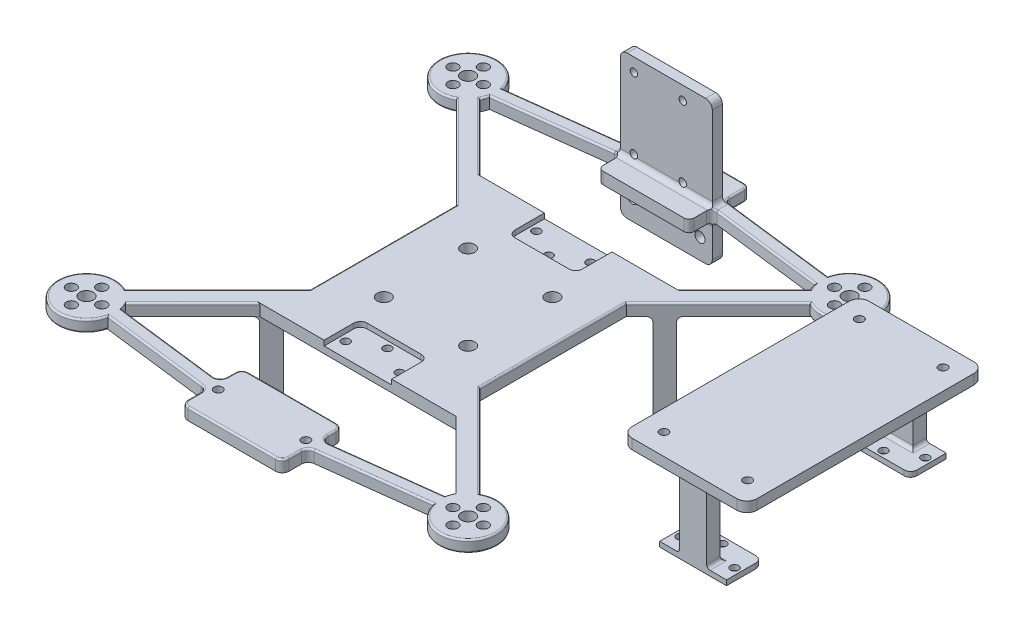
SolidWorks part; units mm, degrees
ref_plane "Front Plane" through (0, 0, 0) normal (0, 0, 1) x (1, 0, 0)
ref_plane "Top Plane" through (0, 0, 0) normal (0, 1, 0) x (1, 0, 0)
ref_plane "Right Plane" through (0, 0, 0) normal (1, 0, 0) x (0, 0, -1)
sketch "Sketch1" plane through (0, 0, 0) normal (0, 1, 0) x (1, 0, 0)
  line L10 (25.2228, 21.7178) -> (52.5194, 49.0143)
  line L11 (29.1718, 32.6991) -> (49.0032, 52.5305)
  line L14 (25.2228, -21.7245) -> (52.5163, -49.018)
  line L15 (29.1386, -32.6991) -> (48.9964, -52.5569)
  line L19 (-25.2228, 21.7178) -> (-52.5879, 49.0829)
  line L20 (-29.1386, -32.6991) -> (-49.0885, -52.649)
  line L22 (-25.2228, -21.7245) -> (-52.6084, -49.1101)
  line L33 (-25.2228, -21.7245) -> (-25.2228, 21.7178)
  line L34 (-16.8093, -62.3977) -> (-48.3224, -58.53)
  line L37 (-8.5504, -52.1195) -> (8.5504, -52.1195)
  line L41 (-17.2966, -58.4661) -> (-48.3352, -54.6566)
  line L42 (25.2228, -21.7245) -> (25.2228, 21.7178)
  line L43 (-48.2996, 54.661) -> (-15.2357, 58.719)
  line L44 (17.1959, -58.4785) -> (48.2122, -54.6717)
  line L45 (16.7086, -62.4101) -> (48.2307, -58.5412)
  line L46 (-29.1718, 32.6991) -> (29.1718, 32.6991)
  line L47 (-29.1386, -32.6991) -> (29.1386, -32.6991)
  line L48 (14.7695, 62.6481) -> (48.2209, 58.5424)
  line L49 (15.135, 58.7314) -> (48.2038, 54.6727)
  line L50 (-13.553, 57.2302) -> (-13.553, 53.6195)
  line L51 (-13.553, 64.1245) -> (-13.553, 68.595)
  line L52 (13.4522, 57.2426) -> (13.4522, 53.6195)
  line L53 (-12.053, 52.1195) -> (11.9522, 52.1195)
  line L54 (-15.053, -56.481) -> (-15.053, -54.1195)
  line L55 (-49.0752, 52.6025) -> (-29.1718, 32.6991)
  line L56 (14.9522, -64.3952) -> (14.9522, -68.095)
  line L57 (-14.8702, 62.6357) -> (-48.3224, 58.53)
  line L58 (12.9522, -70.095) -> (-13.053, -70.095)
  line L64 (-12.053, 70.095) -> (11.9522, 70.095)
  line L65 (13.4522, 68.595) -> (13.4522, 64.1369)
  line L66 (-15.053, -68.095) -> (-15.053, -64.3828)
  line L67 (14.9522, -56.4934) -> (14.9522, -54.1195)
  line L68 (12.9522, -52.1195) -> (-13.053, -52.1195)
  line L69 (14.9522, -52.1195) -> (14.9522, -58.7538)
  arc A0 (-52.6084, -49.1101) -> (-48.3224, -58.53) centre (-56.6207, -56.6207) ccw
  arc A1 (52.5194, 49.0143) -> (48.2209, 58.5424) centre (56.5594, 56.5706) ccw
  arc A2 (-49.0752, 52.6025) -> (-48.2996, 54.661) centre (-56.6207, 56.6207) ccw
  arc A3 (48.9964, -52.5569) -> (48.2122, -54.6717) centre (56.5667, -56.5667) ccw
  arc A8 (-48.3352, -54.6566) -> (-49.0885, -52.649) centre (-56.6207, -56.6207) ccw
  arc A9 (48.2307, -58.5412) -> (52.5163, -49.018) centre (56.5667, -56.5667) ccw
  arc A11 (13.4522, 64.1369) -> (14.7695, 62.6481) centre (14.9522, 64.1369) ccw
  arc A12 (15.135, 58.7314) -> (13.4522, 57.2426) centre (14.9522, 57.2426) ccw
  arc A13 (-13.553, 64.1245) -> (-14.8702, 62.6357) centre (-15.053, 64.1245) cw
  arc A14 (-49.0752, 52.6025) -> (-48.2996, 54.661) centre (-56.6207, 56.6207) ccw
  arc A15 (48.2038, 54.6727) -> (49.0032, 52.5305) centre (56.5594, 56.5706) ccw
  arc A16 (-48.2888, 58.5341) -> (-52.5879, 49.0829) centre (-56.6207, 56.6207) ccw
  arc A17 (14.9522, -56.4934) -> (17.1959, -58.4785) centre (16.9522, -56.4934) ccw
  arc A20 (16.7086, -62.4101) -> (14.9522, -64.3952) centre (16.9522, -64.3952) ccw
  arc A21 (-15.2357, 58.719) -> (-13.553, 57.2302) centre (-15.053, 57.2302) cw
  arc A22 (-13.553, 53.6195) -> (-12.053, 52.1195) centre (-12.053, 53.6195) ccw
  arc A23 (11.9522, 52.1195) -> (13.4522, 53.6195) centre (11.9522, 53.6195) ccw
  arc A24 (11.9522, 70.095) -> (13.4522, 68.595) centre (11.9522, 68.595) cw
  arc A25 (-12.053, 70.095) -> (-13.553, 68.595) centre (-12.053, 68.595) ccw
  arc A26 (-15.053, -56.481) -> (-17.2966, -58.4661) centre (-17.053, -56.481) cw
  arc A27 (-15.053, -64.3828) -> (-16.8093, -62.3977) centre (-17.053, -64.3828) ccw
  arc A28 (-13.053, -70.095) -> (-15.053, -68.095) centre (-13.053, -68.095) cw
  arc A29 (12.9522, -70.095) -> (14.9522, -68.095) centre (12.9522, -68.095) ccw
  arc A30 (14.9522, -54.1195) -> (12.9522, -52.1195) centre (12.9522, -54.1195) ccw
  arc A31 (-15.053, -54.1195) -> (-13.053, -52.1195) centre (-13.053, -54.1195) cw
  point P10 (0, 0)
  point P34 (14.9522, -62.6256)
  point P37 (-15.053, -58.7415)
  point P44 (-28.9553, -58.9711)
  point P57 (13.4522, 58.9379)
  dimension "D1" = 2
  dimension "D2" = 1.5
extrude "Boss-Extrude1" add sketch "Sketch1" along normal blind 3.5 contours A16 L19 L33 L22 A0 L34 L45 A9 L14 L42 L10 A1 L48 L50 L57 L49 A15 L11 L46 L55 A2 L43 A13 L41 A8 L20 L47 L15 A3 L44 L37 region at (0.0088, 0, 0.3906)
sketch "Sketch2" plane through (0, 3.5, 0) normal (0, 1, 0) x (1, 0, 0)
  circle A0 centre (-56.6207, 56.6207) radius 2.003
  circle A1 centre (56.6207, 56.6207) radius 2.003
  circle A2 centre (56.6207, -56.6274) radius 2.003
  circle A3 centre (-56.6207, -56.6274) radius 2.003
  circle A6 centre (56.6207, 61.1356) radius 1.498
  circle A7 centre (61.1356, 56.6207) radius 1.495
  circle A8 centre (56.6207, 52.1058) radius 1.5029
  circle A9 centre (52.1058, 56.6207) radius 1.5021
  circle A10 centre (-56.6207, 61.1356) radius 1.498
  circle A11 centre (-52.1058, 56.6207) radius 1.5021
  circle A12 centre (-56.6207, 52.1058) radius 1.5029
  circle A13 centre (-61.1356, 56.6207) radius 1.495
  circle A14 centre (56.6207, -61.1356) radius 1.498
  circle A15 centre (52.1058, -56.6207) radius 1.5021
  circle A16 centre (56.6207, -52.1058) radius 1.5029
  circle A17 centre (61.1356, -56.6207) radius 1.495
  circle A18 centre (-56.6207, -61.1356) radius 1.498
  circle A19 centre (-52.1058, -56.6207) radius 1.5021
  circle A20 centre (-61.1356, -56.6207) radius 1.495
  circle A21 centre (-56.6207, -52.1058) radius 1.5029
  circle A22 centre (-12.2493, 12.2453) radius 1.9968
  circle A23 centre (-12.2493, -12.7715) radius 1.9976
  circle A24 centre (12.7793, -12.7715) radius 1.9993
  circle A25 centre (12.7793, 12.2453) radius 2.0015
extrude "Cut-Extrude1" cut sketch "Sketch2" against normal through all
sketch "Sketch3" plane through (0, 0, 0) normal (0, -1, 0) x (1, 0, 0)
  line L1 (-25.2228, -21.7178) -> (-52.5879, -49.0829) construction
  line L3 (-29.1718, -32.6991) -> (-32.6879, -29.1829)
  line L4 (-29.1718, -32.6991) -> (-25.6556, -29.1829)
  line L5 (-32.6879, -29.1829) -> (-29.1718, -25.6667)
  line L6 (-25.6556, -29.1829) -> (-29.1718, -25.6667)
  line L7 (32.6879, -29.1829) -> (29.1718, -25.6667)
  line L8 (29.1718, -32.6991) -> (32.6879, -29.1829)
  line L9 (29.1718, -32.6991) -> (25.6556, -29.1829)
  line L10 (25.6556, -29.1829) -> (29.1718, -25.6667)
  line L13 (32.6879, 29.1896) -> (29.1718, 25.6735)
  line L14 (29.1718, 32.7058) -> (32.6879, 29.1896)
  line L15 (25.6556, 29.1896) -> (29.1718, 25.6735)
  line L16 (29.1718, 32.7058) -> (25.6556, 29.1896)
  line L17 (-32.6879, 29.1896) -> (-29.1718, 25.6735)
  line L18 (-29.1718, 32.7058) -> (-25.6556, 29.1896)
  line L19 (-29.1718, 32.7058) -> (-32.6879, 29.1896)
  line L20 (-25.6556, 29.1896) -> (-29.1718, 25.6735)
extrude "Boss-Extrude2" add sketch "Sketch3" along normal blind 30 and the other way blind 2.5
fillet "Fillet1" radius 1.5 8 edges at (30.9299, 0, -30.941) (-27.4137, 0, 27.4316) (30.9299, 0, 30.9477) (-27.4137, 0, -27.4248) (-30.9299, 0, 30.9477) (27.4137, 0, 27.4316) (-30.9299, 0, -30.941) (27.4137, 0, -27.4248)
sketch "Sketch4" plane through (0, 3.5, 0) normal (0, 1, 0) x (1, 0, 0)
  line L8 (-13.885, 59.0576) -> (13.4118, 59.0576)
  line L9 (-13.885, 59.0576) -> (-13.885, 62.0613)
  line L10 (-13.885, 62.0613) -> (13.4118, 62.0613)
  line L11 (13.4118, 59.0576) -> (13.4118, 62.0613)
extrude "Boss-Extrude3" add sketch "Sketch4" along normal blind 27 and the other way blind 15.5
fillet "Fillet2" radius 1.5 6 edges at (-0.2366, 0, -59.0576) (13.4118, 3.5, -60.5595) (-0.2366, 3.5, -59.0576) (-13.885, 3.5, -60.5595) (-13.885, 0, -60.5595) (13.4118, 0, -60.5595)
fillet "Fillet3" radius 2 4 edges at (13.4118, -12, -60.5595) (-13.885, -12, -60.5595) (13.4118, 30.5, -60.5595) (-13.885, 30.5, -60.5595)
sketch "Sketch5" plane through (0, 0, -62.0613) normal (0, 0, -1) x (-1, 0, 0)
  circle A3 centre (9.8595, 5.5028) radius 1.1031
  circle A4 centre (-4.6441, 5.5028) radius 1.0992
  circle A5 centre (9.8595, 26.5151) radius 1.0963
  circle A6 centre (-4.6441, 26.5151) radius 1.0933
  circle A7 centre (-9.7641, -6) radius 1.4993
  circle A8 centre (10.2386, -6) radius 1.4966
extrude "Cut-Extrude2" cut sketch "Sketch5" against normal up to next
fillet "Fillet6" radius 0.5 61 edges at (-14.7161, 3.6574, -58.6919) (-15.3102, 3.5019, -58.7099) (14.5178, 3.5527, -58.6783) (15.0236, 3.5, -58.7409) (32.7041, 3.5, 56.5751) (-0.0504, 3.5, 52.1195) (32.4696, 3.5, 60.4757) (-31.5795, 0, -60.5849) (-13.9296, 0, -63.1306) (-13.553, 0, -66.3598) (-13.1136, 0, -69.6557) (31.4952, 0, -60.5953) (13.8288, 0, -63.1429) (13.4522, 0, -66.366) (13.0129, 0, -69.6557) (-31.5795, 3.5, -60.5849) (-13.9296, 3.5, -63.1306) (-13.553, 3.5, -66.3598) (-13.1136, 3.5, -69.6557) (-0.0504, 3.5, -70.095) (13.0129, 3.5, -69.6557) (13.4522, 3.5, -66.366) (13.8288, 3.5, -63.1429) (-31.8423, 3.5, -56.6808) (-48.6209, 3.5, -53.6067) (31.6694, 3.5, -56.7021) (48.5317, 3.5, -53.5748) (39.0875, 3.5, -42.6148) (-39.1235, 3.5, -42.6508) (38.8711, 3.5, -35.366) (25.2228, 3.5, 0.0034) (38.8696, 3.5, 35.3713) (64.3788, 0, 60.0823) (64.3788, 3.5, 60.0823) (-39.1136, 3.5, 42.674) (-32.8159, 3.5, 56.5614) (-32.5659, 3.5, 60.4638) (-64.3713, 0, 60.1472) (-64.3713, 3.5, 60.1472) (-38.9156, 3.5, 35.4173) (-25.2228, 3.5, 0.0034) (-38.9054, 3.5, -35.4003) (-64.4022, 3.5, -60.1603) (-64.4022, 0, -60.1603) (64.3699, 0, -60.0942) (-0.0504, 0, -70.095) (31.4952, 3.5, -60.5953) (64.3699, 3.5, -60.0942) (15.627, 3.5, 57.9912) (14.9522, 3.5, 55.3064) (14.3664, 3.5, 52.7053) (-14.4672, 3.5, 52.7053) (-15.053, 3.5, 55.3003) (-15.7277, 3.5, 57.9789) (15.4544, 3.5, 63.0699) (14.9522, 3.5, 66.2451) (14.3664, 3.5, 69.5092) (-0.0504, 3.5, 70.095) (-14.4672, 3.5, 69.5092) (-15.053, 3.5, 66.2389) (-15.5551, 3.5, 63.0575)
sketch "Sketch6" plane through (0, 3.5, 0) normal (0, 1, 0) x (1, 0, 0)
  line L4 (10.0048, -23.9249) -> (10.0048, -32.6991)
  line L5 (-29.8789, 32.6991) -> (29.8789, 32.6991) construction
  line L6 (10.0048, -32.6991) -> (-10.0395, -32.6991)
  line L7 (-10.0395, -32.6991) -> (-10.0395, -23.9249)
  line L8 (-8.0395, -21.9249) -> (8.0048, -21.9249)
  line L10 (-8.0395, 21.9249) -> (8.0048, 21.9249)
  line L11 (10.0048, 23.9249) -> (10.0048, 32.6991)
  line L12 (10.0048, 32.6991) -> (-10.0395, 32.6991)
  line L13 (-10.0395, 32.6991) -> (-10.0395, 23.9249)
  arc A0 (8.0048, 21.9249) -> (10.0048, 23.9249) centre (8.0048, 23.9249) ccw
  arc A1 (-10.0395, 23.9249) -> (-8.0395, 21.9249) centre (-8.0395, 23.9249) ccw
  arc A2 (8.0048, -21.9249) -> (10.0048, -23.9249) centre (8.0048, -23.9249) cw
  arc A3 (-10.0395, -23.9249) -> (-8.0395, -21.9249) centre (-8.0395, -23.9249) cw
  dimension "D1" = 2
extrude "Cut-Extrude3" cut sketch "Sketch6" against normal blind 1.5
sketch "Sketch7" plane through (0, 2, 0) normal (0, 1, 0) x (1, 0, 0)
  circle A0 centre (-8.0479, 28.312) radius 1.205
  circle A1 centre (-0.0173, 23.9294) radius 1.1998
  circle A2 centre (8.0011, 28.312) radius 1.205
  circle A3 centre (8.0011, -28.312) radius 1.205
  circle A4 centre (-0.0173, -23.9294) radius 1.1998
  circle A5 centre (-8.0479, -28.312) radius 1.205
extrude "Cut-Extrude5" cut sketch "Sketch7" against normal through all
sketch "Sketch10" plane through (0, 3.5, 0) normal (0, 1, 0) x (1, 0, 0)
  circle A0 centre (-13.053, -61.1073) radius 1.2524
  circle A1 centre (12.9522, -61.1073) radius 1.2475
extrude "Cut-Extrude6" cut sketch "Sketch10" against normal through all
sketch "Sketch11" plane through (0, 0, 0) normal (0, 1, 0) x (1, 0, 0)
  line L4 (89.4618, 32.5991) -> (89.4618, 23.9249)
  line L5 (107.4062, 22.0249) -> (91.3618, 22.0249)
  line L6 (109.3062, 32.5991) -> (109.3062, 23.9249)
  line L7 (89.4618, 32.5991) -> (109.3062, 32.5991)
  line L10 (109.3062, -32.5991) -> (109.3062, -23.9249)
  line L11 (107.4062, -22.0249) -> (91.3618, -22.0249)
  line L12 (89.4618, -32.5991) -> (109.3062, -32.5991)
  line L13 (89.4618, -32.5991) -> (89.4618, -23.9249)
  arc A2 (91.3618, 22.0249) -> (89.4618, 23.9249) centre (91.3618, 23.9249) cw
  arc A3 (107.4062, 22.0249) -> (109.3062, 23.9249) centre (107.4062, 23.9249) ccw
  arc A4 (107.4062, -22.0249) -> (109.3062, -23.9249) centre (107.4062, -23.9249) cw
  arc A5 (91.3618, -22.0249) -> (89.4618, -23.9249) centre (91.3618, -23.9249) ccw
extrude "Boss-Extrude4" add sketch "Sketch11" along normal blind 1.5 separate body
sketch "Sketch12" plane through (0, 1.5, 0) normal (0, 1, 0) x (1, 0, 0)
  circle A0 centre (91.3535, 28.3053) radius 1.205
  circle A1 centre (99.384, 23.9228) radius 1.1998
  circle A2 centre (107.4025, 28.3053) radius 1.205
  circle A3 centre (107.4025, -28.3186) radius 1.205
  circle A4 centre (99.384, -23.9361) radius 1.1998
  circle A5 centre (91.3535, -28.3186) radius 1.205
extrude "Cut-Extrude7" cut sketch "Sketch12" against normal through all
sketch "Sketch13" plane through (0, 1.5, 0) normal (0, 1, 0) x (1, 0, 0)
  line L0 (95.3874, 32.5991) -> (95.3874, 28.6039)
  line L2 (109.3062, 32.5991) -> (89.4618, 32.5991) construction
  line L3 (95.3874, 32.5991) -> (103.3936, 32.5991)
  line L4 (95.3874, 28.6039) -> (103.3936, 28.6039)
  line L5 (103.3936, 28.6039) -> (103.3936, 32.5991)
  line L10 (95.3874, -32.5991) -> (95.3874, -28.6039)
  line L11 (95.3874, -32.5991) -> (103.3936, -32.5991)
  line L12 (103.3936, -28.6039) -> (103.3936, -32.5991)
  line L13 (95.3874, -28.6039) -> (103.3936, -28.6039)
extrude "Boss-Extrude5" add sketch "Sketch13" along normal blind 23.5 and the other way blind 1.253
fillet "Fillet7" radius 1 3 edges at (103.3936, 1.5, 30.6015) (99.3905, 1.5, 28.6039) (95.3874, 1.5, 30.6015)
fillet "Fillet8" radius 1 3 edges at (95.3874, 1.5, -30.6015) (99.3905, 1.5, -28.6039) (103.3936, 1.5, -30.6015)
sketch "Sketch14" plane through (0, 25, 0) normal (0, 1, 0) x (1, 0, 0)
  line L0 (80.8723, 35.1637) -> (80.8723, -35.1882)
  line L3 (80.8723, 35.1637) -> (117.9365, 35.1637)
  line L4 (80.8723, -35.1882) -> (117.9365, -35.1882)
  line L5 (117.9365, -35.1882) -> (117.9365, 35.1637)
extrude "Boss-Extrude6" add sketch "Sketch14" along normal blind 1.5 and the other way blind 1.5
fillet "Fillet9" radius 2 8 edges at (99.3905, 23.5, -32.5991) (95.3874, 23.5, -30.6015) (99.3905, 23.5, 28.6039) (95.3874, 23.5, 30.6015) (99.3905, 23.5, 32.5991) (99.3905, 23.5, -28.6039) (103.3936, 23.5, -30.6015) (103.3936, 23.5, 30.6015)
fillet "Fillet10" radius 3 4 edges at (80.8723, 25, -35.1637) (117.9365, 25, -35.1637) (80.8723, 25, 35.1882) (117.9365, 25, 35.1882)
sketch "Sketch15" plane through (0, 26.5, 0) normal (0, 1, 0) x (1, 0, 0)
  circle A0 centre (86.9844, 29.1301) radius 1.2706
  circle A1 centre (111.8244, 29.1301) radius 1.2655
  circle A2 centre (86.9844, -28.8874) radius 1.2458
  circle A3 centre (111.8244, -28.8874) radius 1.2607
extrude "Cut-Extrude8" cut sketch "Sketch15" against normal up to next (3 mm away)
